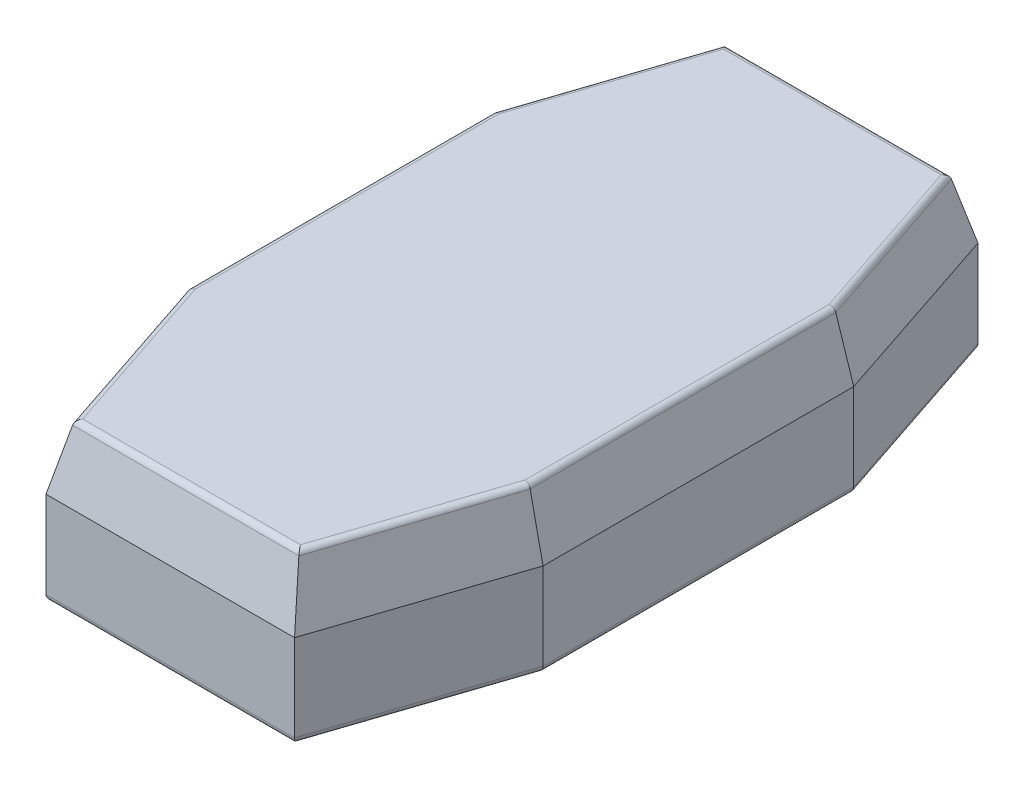
SolidWorks part; units mm, degrees
ref_plane "Front Plane" through (0, 0, 0) normal (0, 0, 1) x (1, 0, 0)
ref_plane "Top Plane" through (0, 0, 0) normal (0, 1, 0) x (1, 0, 0)
ref_plane "Right Plane" through (0, 0, 0) normal (1, 0, 0) x (0, 0, -1)
sketch "Sketch1" plane through (0, 0, 0) normal (0, 1, 0) x (1, 0, 0)
  line L0 (-7.62, 6.35) -> (-5.08, 13.97)
  line L1 (-5.08, 13.97) -> (5.08, 13.97)
  line L2 (-7.62, 6.35) -> (-7.62, -6.35)
  line L3 (-5.08, -13.97) -> (5.08, -13.97)
  line L4 (7.62, 6.35) -> (7.62, -6.35)
  line L5 (-7.62, 13.97) -> (7.62, -13.97) construction
  line L6 (-7.62, -13.97) -> (7.62, 13.97) construction
  line L7 (5.08, 13.97) -> (7.62, 6.35)
  line L8 (5.08, -13.97) -> (7.62, -6.35)
  line L9 (-7.62, -6.35) -> (-5.08, -13.97)
  point P0 (0, 0)
  dimension "D1" = 15.24
  dimension "D2" = 27.94
  dimension "D3" = 2.54
  dimension "D4" = 7.62
  dimension "D5" = 2.54
  dimension "D6" = 7.62
  dimension "D7" = 2.54
  dimension "D8" = 7.62
  dimension "D9" = 7.62
  dimension "D10" = 2.54
extrude "Boss-Extrude1" add sketch "Sketch1" along normal blind 2.54 draft 15
sketch "Stem" plane through (0, 0, 0) normal (0, -1, 0) x (1, 0, 0)
  line L1 (-0.5625, 2.075) -> (0.5625, 2.075)
  line L2 (-0.5625, 2.075) -> (-0.5625, -2.075)
  line L3 (-0.5625, -2.075) -> (0.5625, -2.075)
  line L4 (0.5625, 2.075) -> (0.5625, -2.075)
  line L5 (-0.5625, 2.075) -> (0.5625, -2.075) construction
  line L6 (-0.5625, -2.075) -> (0.5625, 2.075) construction
  line L7 (2.0625, 0.6625) -> (-2.0625, 0.6625)
  line L8 (2.0625, 0.6625) -> (2.0625, -0.6625)
  line L9 (2.0625, -0.6625) -> (-2.0625, -0.6625)
  line L10 (-2.0625, 0.6625) -> (-2.0625, -0.6625)
  line L11 (2.0625, 0.6625) -> (-2.0625, -0.6625) construction
  line L12 (2.0625, -0.6625) -> (-2.0625, 0.6625) construction
  line L13 (-2.5, 2.5) -> (2.5, 2.5)
  line L14 (-3, 2) -> (-3, -2)
  line L15 (-2.5, -2.5) -> (2.5, -2.5)
  line L16 (3, 2) -> (3, -2)
  line L17 (-3, 2.5) -> (3, -2.5) construction
  line L18 (-3, -2.5) -> (3, 2.5) construction
  arc A0 (-3, -2) -> (-2.5, -2.5) centre (-2.5, -2) ccw
  arc A1 (-2.5, 2.5) -> (-3, 2) centre (-2.5, 2) ccw
  arc A2 (2.5, -2.5) -> (3, -2) centre (2.5, -2) ccw
  arc A3 (2.5, 2.5) -> (3, 2) centre (2.5, 2) cw
  point P0 (0, 0)
  point P6 (0, 0)
  point P11 (0, 0)
  dimension "D7" = 0.5
  dimension "D1" = 4.15
  dimension "D2" = 1.125
  dimension "D3" = 1.325
  dimension "D4" = 4.125
  dimension "D5" = 5
  dimension "D6" = 6
extrude "Boss-Extrude2" add sketch "Stem" along normal blind 3.8 contours A3 L13 A1 L14 A0 L15 A2 L16 L10 L7 L2 L1 L4 L8 L9 L3 region at (0, 0, 2.4219)
fillet "Fillet2" radius 0.1 8 edges at (-2.8536, -3.8, -2.3536) (-3, -3.8, 0) (-2.8536, -3.8, 2.3536) (0, -3.8, 2.5) (2.8536, -3.8, 2.3536) (3, -3.8, 0) (2.8536, -3.8, -2.3536) (0, -3.8, -2.5)
chamfer "Chamfer1" distance 0.2 angle 45 11 edges at (-0.5625, -3.8, -1.3688) (-1.3125, -3.8, -0.6625) (-2.0625, -3.8, 0) (0.5625, -3.8, -1.3688) (1.3125, -3.8, -0.6625) (2.0625, -3.8, 0) (1.3125, -3.8, 0.6625) (0.5625, -3.8, 1.3687) (0, -3.8, 2.075) (-0.5625, -3.8, 1.3687) (-1.3125, -3.8, 0.6625)
sketch "Sketch3" plane through (0, 0, 0) normal (0, -1, 0) x (1, 0, 0)
  line L0 (-7.62, 6.35) -> (-7.62, -6.35)
  line L1 (-7.62, -6.35) -> (-5.08, -13.97)
  line L2 (-5.08, -13.97) -> (5.08, -13.97)
  line L3 (5.08, -13.97) -> (7.62, -6.35)
  line L4 (7.62, -6.35) -> (7.62, 6.35)
  line L5 (7.62, 6.35) -> (5.08, 13.97)
  line L6 (5.08, 13.97) -> (-5.08, 13.97)
  line L7 (-5.08, 13.97) -> (-7.62, 6.35)
  line L44 (-6.35, -6.1439) -> (-4.1646, -12.7)
  line L45 (-4.1646, -12.7) -> (4.1646, -12.7)
  line L46 (4.1646, -12.7) -> (6.35, -6.1439)
  line L47 (6.35, -6.1439) -> (6.35, 6.1439)
  line L48 (6.35, 6.1439) -> (4.1646, 12.7)
  line L49 (4.1646, 12.7) -> (-4.1646, 12.7)
  line L50 (-4.1646, 12.7) -> (-6.35, 6.1439)
  line L51 (-6.35, 6.1439) -> (-6.35, -6.1439)
  line L52 (-6.35, -6.1439) -> (-4.1646, -12.7)
  line L53 (-4.1646, -12.7) -> (4.1646, -12.7)
  line L54 (4.1646, -12.7) -> (6.35, -6.1439)
  line L55 (6.35, -6.1439) -> (6.35, 6.1439)
  line L56 (6.35, 6.1439) -> (4.1646, 12.7)
  line L57 (4.1646, 12.7) -> (-4.1646, 12.7)
  line L58 (-4.1646, 12.7) -> (-6.35, 6.1439)
  line L59 (-6.35, 6.1439) -> (-6.35, -6.1439)
  dimension "D1" = 1.27
extrude "Boss-Extrude3" add sketch "Sketch3" along normal blind 3.8
fillet "Fillet3" radius 0.25 16 edges at (0, -3.8, -12.7) (5.2573, -3.8, -9.422) (6.35, -3.8, 0) (5.2573, -3.8, 9.422) (0, -3.8, 12.7) (-5.2573, -3.8, 9.422) (-6.35, -3.8, 0) (-5.2573, -3.8, -9.422) (0, -3.8, 13.97) (6.35, -3.8, 10.16) (7.62, -3.8, 0) (6.35, -3.8, -10.16) (0, -3.8, -13.97) (-6.35, -3.8, -10.16) (-7.62, -3.8, 0) (-6.35, -3.8, 10.16)
fillet "Fillet5" radius 0.5 16 edges at (0, 0, 2.5) (-2.8536, 0, 2.3536) (-3, 0, 0) (-2.8536, 0, -2.3536) (0, 0, -2.5) (2.8536, 0, -2.3536) (3, 0, 0) (2.8536, 0, 2.3536) (-5.2573, 0, 9.422) (0, 0, 12.7) (5.2573, 0, 9.422) (6.35, 0, 0) (5.2573, 0, -9.422) (0, 0, -12.7) (-5.2573, 0, -9.422) (-6.35, 0, 0)
fillet "Fillet6" radius 0.1 12 edges at (-1.3125, 0, 0.6625) (-0.5625, 0, 1.3687) (0, 0, 2.075) (0.5625, 0, 1.3687) (1.3125, 0, 0.6625) (2.0625, 0, 0) (1.3125, 0, -0.6625) (0.5625, 0, -1.3688) (0, 0, -2.075) (-0.5625, 0, -1.3688) (-1.3125, 0, -0.6625) (-2.0625, 0, 0)
fillet "Fillet7" radius 0.25 8 edges at (5.7644, 2.54, -9.7645) (6.9394, 2.54, 0) (5.7644, 2.54, 9.7645) (0, 2.54, 13.2894) (-5.7644, 2.54, 9.7645) (-6.9394, 2.54, 0) (-5.7644, 2.54, -9.7645) (0, 2.54, -13.2894)
